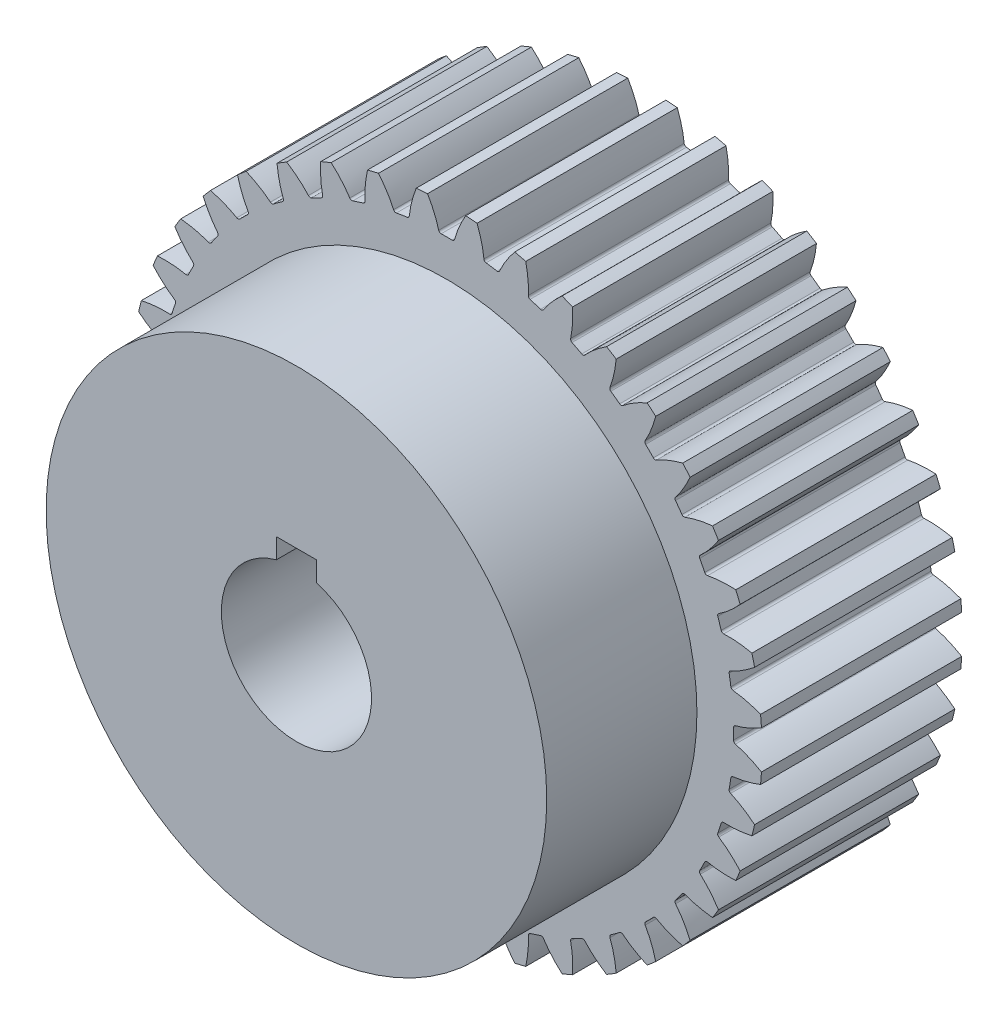
SolidWorks part; units mm, degrees
ref_plane "Front Plane" through (0, 0, 0) normal (0, 0, 1) x (1, 0, 0)
ref_plane "Top Plane" through (0, 0, 0) normal (0, 1, 0) x (1, 0, 0)
ref_plane "Right Plane" through (0, 0, 0) normal (1, 0, 0) x (0, 0, -1)
sketch "Sketch1" plane through (0, 0, 0) normal (0, 0, 1) x (1, 0, 0)
  line L0 (0, 30) -> (0, -30) construction
  line L1 (0, -30) -> (8.8305, -30) construction
  line L2 (0, -30) -> (9.6418, -26.4907) construction
  line L3 (0, 0) -> (9.6418, -26.4907)
  line L4 (0, 0) -> (-28.1284, 0) construction
  line L5 (-28.1284, 1.875) -> (-28.1284, -1.875) construction
  line L6 (-28.1284, 1.875) -> (0, 0) construction
  line L7 (0, 0) -> (-28.1284, -1.875) construction
  line L8 (0, 0) -> (-20.6686, 19.1711) construction
  line L9 (0, 0) -> (-17.9401, 21.7456) construction
  line L10 (0, 0) -> (-14.894, 23.9351) construction
  line L11 (0, 0) -> (-11.5842, 25.7007) construction
  line L12 (0, 0) -> (-8.0692, 27.0113) construction
  line L13 (0, 0) -> (-4.4113, 27.8435) construction
  line L14 (-4.4113, 27.8435) -> (-0.7075, 28.4303) construction
  line L15 (-8.0692, 27.0113) -> (-0.883, 29.158) construction
  line L16 (-11.5842, 25.7007) -> (-1.3279, 30.3236) construction
  line L17 (-14.894, 23.9351) -> (-2.1584, 31.86) construction
  line L18 (-17.9401, 21.7456) -> (-3.4769, 33.6778) construction
  line L19 (-20.6686, 19.1711) -> (-5.3675, 35.6673) construction
  circle A0 centre (0, 0) radius 28.1908 construction
  arc A1 (1.1779, 29.9769) -> (-1.1779, 29.9769) centre (0, 0) ccw construction
  circle A2 centre (0, 30) radius 1.1781 construction
  circle A3 centre (0, 0) radius 28.6595
  circle A4 centre (0, 0) radius 31.5
  circle A5 centre (0, 0) radius 7.5
  circle A6 centre (0, 0) radius 25
  spline S0 degree 3 poles (-5.3675, 35.6673) (-4.1503, 34.5369) (-2.6529, 32.8286) (-1.3674, 30.4884) (-0.9147, 29.3232) (-0.6834, 28.4341) (-0.6286, 27.5171) (-0.6989, 26.269) (-1.1981, 23.646) (-2.0942, 21.5586) (-2.9023, 20.1072) knots 0 0 0 0 0.285711 0.385711 0.45714 0.5 0.54286 0.614289 0.714289 1 1 1 1
  spline S1 degree 3 poles (5.3675, 35.6673) (4.1503, 34.5369) (2.6529, 32.8286) (1.3674, 30.4884) (0.9147, 29.3232) (0.6834, 28.4341) (0.6286, 27.5171) (0.6989, 26.269) (1.1981, 23.646) (2.0942, 21.5586) (2.9023, 20.1072) knots 0 0 0 0 0.285711 0.385711 0.45714 0.5 0.54286 0.614289 0.714289 1 1 1 1
  point P3 (-2.9023, 20.1072)
  point P4 (0, 0)
  point P16 (-28.1284, 0)
  point P27 (-1.7192, 22.5838)
  point P28 (-1.0272, 24.72)
  point P29 (-0.7123, 26.438)
  point P30 (-0.6494, 27.684)
  dimension "D4" = 2.3562
  dimension "D17" = 63
  dimension "D18" = 57.3191
  dimension "D19" = 15
  dimension "D20" = 50
  dimension "D1" = 20
  dimension "D2" = 60
  dimension "D3" = 90
  dimension "D5" = 3.75
  dimension "D6" = 7.63
  dimension "D7" = 7.63
  dimension "D8" = 7.63
  dimension "D9" = 7.63
  dimension "D10" = 7.63
  dimension "D11" = 3.75
  dimension "D12" = 7.5
  dimension "D13" = 11.25
  dimension "D14" = 15
  dimension "D15" = 18.75
  dimension "D16" = 22.5
extrude "Boss-Extrude1" add sketch "Sketch1" along normal blind 20 contours A4
extrude "Cut-Extrude2" cut sketch "Sketch1<5>" along normal through all contours S1 A4 S0 A3 region at (0, 30.2907, 0)
sketch "Sketch1<5>" plane through (0, 0, 0) normal (0, 0, 1) x (1, 0, 0) same geometry as "Sketch1"
fillet "Fillet1" radius 0.25 2 edges at (0.7485, 28.6498, 10) (-0.7485, 28.6498, 10)
pattern_circular "CirPattern1" count 40 over 360 about axis through (0, 0, 20) along (0, 0, -1) of "Cut-Extrude2", "Fillet1" reverse direction yes
extrude "Boss-Extrude2" add sketch "Sketch1<8>" along normal blind 35 contours A6
sketch "Sketch1<8>" plane through (0, 0, 0) normal (0, 0, 1) x (1, 0, 0) same geometry as "Sketch1"
sketch "Sketch2" plane through (0, 0, 0) normal (0, 0, -1) x (-1, 0, 0)
  circle A0 centre (0, 0) radius 7.5
  dimension "D1" = 15
extrude "Cut-Extrude4" cut sketch "Sketch2" against normal through all
sketch "Sketch6" plane through (0, 0, 35) normal (0, 0, 1) x (1, 0, 0)
  line L0 (0, -7.5) -> (0, 7.5) construction
  line L1 (-2, 7.2284) -> (2, 7.2284)
  line L2 (-2, 7.2284) -> (-2, 9.2284)
  line L3 (-2, 9.2284) -> (2, 9.2284)
  line L4 (2, 9.2284) -> (2, 7.2284)
  circle A0 centre (0, 0) radius 7.5 construction
  point P7 (0, 0)
  point P9 (0, 7.2284)
  dimension "D1" = 4
  dimension "D2" = 2
extrude "Cut-Extrude5" cut sketch "Sketch6" against normal through all
equation "\"boss\"= 50mm"
equation "\"bore\"= 15mm"
equation "\"pcd\"= 60mm"
equation "\"d\"= 63mm"
equation "\"e\"= 7.63"
equation "\"x\"= 3.75"
equation "\"y\"= 1"
equation "\"z\"= 1"
equation "\"D2@Sketch1\"=\"pcd\""
equation "\"D4@Sketch1\"=3/4*pi"
equation "\"D6@Sketch1\"=\"e\""
equation "\"D7@Sketch1\"=\"e\""
equation "\"D8@Sketch1\"=\"e\""
equation "\"D9@Sketch1\"=\"e\""
equation "\"D10@Sketch1\"=\"e\""
equation "\"D12@Sketch1\"=\"x\"*2"
equation "\"D13@Sketch1\"=\"x\"*3"
equation "\"D14@Sketch1\"=\"x\"*4"
equation "\"D15@Sketch1\"=\"x\"*5"
equation "\"D16@Sketch1\"=\"x\"*6"
equation "\"D17@Sketch1\"=\"d\""
equation "\"D19@Sketch1\"=\"bore\""
equation "\"D20@Sketch1\"=\"boss\""
equation "\"D1@Sketch2\"=\"bore\""
